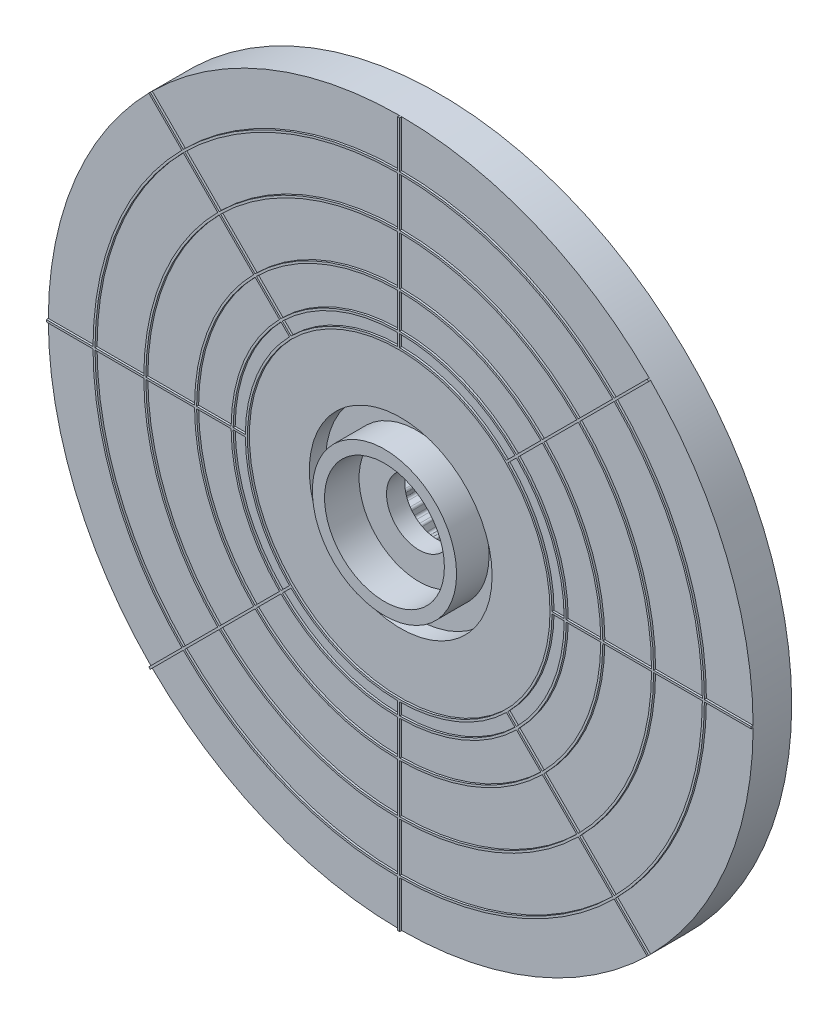
SolidWorks part; units mm, degrees
material "PVC hart"
ref_plane "Ebene vorne" through (0, 0, 0) normal (0, 0, 1) x (1, 0, 0)
ref_plane "Ebene oben" through (0, 0, 0) normal (0, 1, 0) x (1, 0, 0)
ref_plane "Ebene rechts" through (0, 0, 0) normal (1, 0, 0) x (0, 0, -1)
sketch "Skizze5" plane through (0, 0, 0) normal (1, 0, 0) x (0, 0, -1)
  line L0 (0, 0) -> (31.9699, 0) construction
  line L1 (0.75, 4.1) -> (3.1, 4.1)
  line L2 (3.1, 4.1) -> (3.1, 2.9)
  line L3 (3.1, 2.9) -> (0, 2.9)
  line L4 (0, 2.9) -> (0, 1.6)
  line L5 (0, 1.6) -> (-0.9, 1.6)
  line L6 (-0.9, 1.6) -> (-0.9, 2.95)
  line L7 (-0.9, 2.95) -> (-2.6, 2.95)
  line L8 (-2.6, 2.95) -> (-2.6, 3.55)
  line L9 (-2.6, 3.55) -> (-1, 3.55)
  line L10 (-1, 3.55) -> (-1, 4.5)
  line L11 (-1, 4.5) -> (-1.8, 4.5)
  line L12 (-1.8, 4.5) -> (-1.8, 20)
  line L13 (-1.8, 20) -> (0.1, 20)
  line L14 (0.1, 20) -> (0.1, 4.75)
  line L15 (0, 1.6) -> (0, 0) construction
  line L16 (0.1, 4.75) -> (0.75, 4.1)
  dimension "D1" = 8.2
  dimension "D2" = 5.8
  dimension "D3" = 135
  dimension "D4" = 3
  dimension "D5" = 1.9
  dimension "D6" = 9
  dimension "D7" = 7.1
  dimension "D8" = 5.9
  dimension "D9" = 3.2
  dimension "D10" = 3.1
  dimension "D11" = 5.7
  dimension "D12" = 1.7
  dimension "D13" = 40
  dimension "D14" = 0.8
  dimension "D15" = 9.5
revolve "Rotation2" add sketch "Skizze5" angle 360 about L0
ref_axis "Rotationsachse" through (0, 0, 0) along (0, 0, 1)
sketch "Skizze4" plane through (0, 0, -3.1) normal (0, 0, 1) x (1, 0, 0)
  line L0 (0, 0) -> (-0.3635, 2.8771) construction
  line L1 (-0.2786, 2.847) -> (-0.0723, 2.6309)
  line L2 (0.2786, 2.847) -> (0.0723, 2.6309)
  line L3 (0.3635, 2.8771) -> (0, 0) construction
  line L4 (0, 2.9) -> (0, 0) construction
  circle A0 centre (0, 0) radius 2.9 construction
  arc A2 (-0.3635, 2.8771) -> (0.3635, 2.8771) centre (0, 0) cw
  circle A3 centre (0, 0) radius 2.6 construction
  arc A4 (-0.0723, 2.6309) -> (0.0723, 2.6309) centre (0, 2.7) ccw
  arc A5 (-0.3635, 2.8771) -> (-0.2786, 2.847) centre (-0.3509, 2.7779) cw
  arc A6 (0.3635, 2.8771) -> (0.2786, 2.847) centre (0.3509, 2.7779) ccw
  point P14 (0, 2.6)
  dimension "D2" = 5.2
  dimension "D3" = 0.1
  dimension "D1" = 14.4
extrude "Aufsatz-Linear austragen4" add sketch "Skizze4" along normal up to surface (3.1 mm away) up to face at (2.9, 0, 0)
pattern_circular "Kreismuster1" count 25 over 360 about axis through (0, 0, 0) along (0, 0, 1) of "Aufsatz-Linear austragen4"
sketch "Skizze6" plane through (0, 0, 1.8) normal (0, 0, 1) x (1, 0, 0)
  circle A0 centre (0, 0) radius 17.35
  dimension "D1" = 34.7
extrude "Schnitt-Linear austragen1" cut sketch "Skizze6" against normal through all flip side to cut
sketch "Skizze7" plane through (0, 0, 1.8) normal (0, 0, 1) x (1, 0, 0)
  line L0 (0, 17.35) -> (0, 7.5)
  line L1 (7.5, 0) -> (17.35, 0)
  line L2 (0, -7.5) -> (0, -17.35)
  line L3 (-7.5, 0) -> (-17.35, 0)
  line L4 (5.3033, 5.3033) -> (12.2683, 12.2683)
  line L5 (5.3033, -5.3033) -> (12.2683, -12.2683)
  line L6 (-5.3033, -5.3033) -> (-12.2683, -12.2683)
  line L7 (-5.3033, 5.3033) -> (-12.2683, 12.2683)
  line L8 (-17.35, 0) -> (-12.2683, 12.2683) construction
  line L9 (0, 17.35) -> (-12.2683, 12.2683) construction
  line L10 (0, 17.35) -> (12.2683, 12.2683) construction
  line L11 (12.2683, 12.2683) -> (17.35, 0) construction
  line L12 (17.35, 0) -> (12.2683, -12.2683) construction
  line L13 (12.2683, -12.2683) -> (0, -17.35) construction
  line L14 (0, -17.35) -> (-12.2683, -12.2683) construction
  line L15 (-12.2683, -12.2683) -> (-17.35, 0) construction
  circle A0 centre (0, 0) radius 10
  circle A1 centre (0, 0) radius 12.5
  circle A2 centre (0, 0) radius 15
  circle A3 centre (0, 0) radius 7.5
  circle A4 centre (0, 0) radius 8.2
  circle A5 centre (0, 0) radius 17.35 construction
  dimension "D1" = 15
  dimension "D2" = 16.4
  dimension "D3" = 20
  dimension "D4" = 25
  dimension "D5" = 30
extrude "Linear-Austragen-Dünn1" add sketch "Skizze7" along normal blind 0.1 thin contours A3 | A4 | A0 | A1 | A2 | L0 | L7 | L3 | L6 | L2 | L5 | L1 | L4 thin type mid plane wall 0.1
sketch "Skizze9" [suppressed] plane through (0, 0, 1.8) normal (0, 0, 1) x (1, 0, 0)
  line L0 (-4.275, 7.1726) -> (-2.3589, 17.3923)
  line L1 (2.3589, 17.3923) -> (4.275, 7.1726)
  line L2 (0, 16.95) -> (0, -16.95) construction
  line L3 (-4.275, -7.1726) -> (-2.3589, -17.3923)
  line L4 (7.65, 0) -> (10.7, 0) construction
  line L5 (10.7, 0) -> (13.75, 0) construction
  line L6 (13.75, 0) -> (16.95, 0)
  line L7 (16.95, 0) -> (20, 0) construction
  line L8 (2.3589, -17.3923) -> (4.275, -7.1726)
  arc A0 (-2.3589, 17.3923) -> (2.3589, 17.3923) centre (0, 16.95) cw
  circle A1 centre (0, 0) radius 20 construction
  circle A2 centre (0, -7.65) radius 0.9
  circle A3 centre (0, 0) radius 16.95 construction
  circle A4 centre (0, 0) radius 8.35 construction
  circle A6 centre (0, 0) radius 6.75 construction
  circle A7 centre (0, 16.95) radius 0.9
  circle A8 centre (0, 13.75) radius 0.9
  circle A9 centre (0, 10.7) radius 0.9
  circle A10 centre (0, 7.65) radius 0.9
  circle A11 centre (0, 0) radius 13.75 construction
  circle A12 centre (0, 0) radius 10.7 construction
  circle A13 centre (0, 0) radius 7.65 construction
  circle A14 centre (0, -10.7) radius 0.9
  circle A15 centre (0, -13.75) radius 0.9
  circle A16 centre (0, -16.95) radius 0.9
  arc A17 (-2.3589, -17.3923) -> (2.3589, -17.3923) centre (0, -16.95) ccw
  arc A18 (-4.275, 7.1726) -> (-4.275, -7.1726) centre (33.9807, 0) ccw
  arc A19 (4.275, -7.1726) -> (4.275, 7.1726) centre (-33.9807, 0) ccw
  dimension "D1" = 2.4
  dimension "D3" = 15.3
  dimension "D4" = 16.7
  dimension "D6" = 13.5
  dimension "D8" = 1.8
  dimension "D2" = 8.55
  dimension "D7" = 3.2
extrude "2er" [suppressed] cut sketch "Skizze9" against normal through all flip side to cut
sketch "Skizze8" [suppressed] plane through (0, 0, 1.8) normal (0, 0, 1) x (1, 0, 0)
  line L0 (-4.275, 7.1726) -> (-2.3589, 17.3923)
  line L1 (2.3589, 17.3923) -> (4.275, 7.1726)
  line L2 (0, 16.95) -> (0, -16.95) construction
  line L3 (0, 0) -> (14.1421, 14.1421) construction
  line L4 (7.65, 0) -> (10.7, 0) construction
  line L5 (10.7, 0) -> (13.75, 0) construction
  line L6 (13.75, 0) -> (16.95, 0)
  line L7 (16.95, 0) -> (20, 0) construction
  line L8 (7.1726, 4.275) -> (17.3923, 2.3589)
  line L9 (17.3923, -2.3589) -> (7.1726, -4.275)
  line L10 (4.275, -7.1726) -> (2.3589, -17.3923)
  line L11 (-2.3589, -17.3923) -> (-4.275, -7.1726)
  line L12 (-7.1726, -4.275) -> (-17.3923, -2.3589)
  line L13 (-17.3923, 2.3589) -> (-7.1726, 4.275)
  arc A0 (-2.3589, 17.3923) -> (2.3589, 17.3923) centre (0, 16.95) cw
  arc A1 (4.275, 7.1726) -> (7.1726, 4.275) centre (6.3522, 6.3522) ccw
  circle A2 centre (0, 0) radius 8.9834 construction
  circle A3 centre (0, 0) radius 16.95 construction
  circle A4 centre (0, 0) radius 8.35 construction
  circle A5 centre (0, 0) radius 20 construction
  circle A6 centre (0, 0) radius 6.75 construction
  circle A7 centre (0, 16.95) radius 0.9
  circle A8 centre (0, 13.75) radius 0.9
  circle A9 centre (0, 10.7) radius 0.9
  circle A10 centre (0, 7.65) radius 0.9
  circle A11 centre (0, 0) radius 13.75 construction
  circle A12 centre (0, 0) radius 10.7 construction
  circle A13 centre (0, 0) radius 7.65 construction
  arc A14 (17.3923, 2.3589) -> (17.3923, -2.3589) centre (16.95, 0) cw
  circle A15 centre (16.95, 0) radius 0.9
  circle A16 centre (13.75, 0) radius 0.9
  circle A17 centre (10.7, 0) radius 0.9
  circle A18 centre (7.65, 0) radius 0.9
  arc A19 (7.1726, -4.275) -> (4.275, -7.1726) centre (6.3522, -6.3522) ccw
  arc A20 (2.3589, -17.3923) -> (-2.3589, -17.3923) centre (0, -16.95) cw
  circle A21 centre (0, -16.95) radius 0.9
  circle A22 centre (0, -13.75) radius 0.9
  circle A23 centre (0, -10.7) radius 0.9
  circle A24 centre (0, -7.65) radius 0.9
  arc A25 (-4.275, -7.1726) -> (-7.1726, -4.275) centre (-6.3522, -6.3522) ccw
  arc A26 (-17.3923, -2.3589) -> (-17.3923, 2.3589) centre (-16.95, 0) cw
  circle A27 centre (-16.95, 0) radius 0.9
  circle A28 centre (-13.75, 0) radius 0.9
  circle A29 centre (-10.7, 0) radius 0.9
  circle A30 centre (-7.65, 0) radius 0.9
  arc A31 (-7.1726, 4.275) -> (-4.275, 7.1726) centre (-6.3522, 6.3522) ccw
  point P77 (0, 0)
  dimension "D1" = 2.4
  dimension "D3" = 15.3
  dimension "D4" = 16.7
  dimension "D6" = 13.5
  dimension "D8" = 1.8
  dimension "D2" = 8.55
  dimension "D5" = 45
  dimension "D7" = 3.2
  dimension "D9" = 4
extrude "4er" [suppressed] cut sketch "Skizze8" against normal through all flip side to cut
sketch "Skizze10" [suppressed] plane through (0, 0, 1.8) normal (0, 0, 1) x (1, 0, 0)
  line L0 (7.6, 0) -> (9.9, 0) construction
  line L1 (9.9, 0) -> (12.75, 0) construction
  line L2 (0, 12.75) -> (0, -12.75) construction
  line L3 (-3.4, 5.889) -> (-2.3761, 13.088)
  line L4 (2.3761, 13.088) -> (3.4, 5.889)
  line L5 (-3.4, 5.889) -> (0, 0) construction
  line L6 (0, 0) -> (3.4, 5.889) construction
  line L7 (-3.4, 5.889) -> (3.4, 5.889) construction
  line L8 (3.4, 5.889) -> (10.1465, 8.6017)
  line L9 (12.5225, 4.4862) -> (6.8, 0)
  line L10 (6.8, 0) -> (12.5225, -4.4862)
  line L11 (10.1465, -8.6017) -> (3.4, -5.889)
  line L12 (3.4, -5.889) -> (2.3761, -13.088)
  line L13 (-2.3761, -13.088) -> (-3.4, -5.889)
  line L14 (-3.4, -5.889) -> (-10.1465, -8.6017)
  line L15 (-12.5225, -4.4862) -> (-6.8, 0)
  line L16 (-6.8, 0) -> (-12.5225, 4.4862)
  line L17 (-10.1465, 8.6017) -> (-3.4, 5.889)
  circle A0 centre (0, 0) radius 7.6 construction
  circle A1 centre (0, 0) radius 9.9 construction
  circle A2 centre (0, 0) radius 12.75 construction
  circle A3 centre (0, 7.6) radius 0.9
  circle A4 centre (0, 9.9) radius 0.9
  circle A5 centre (0, 12.75) radius 0.9
  arc A6 (-2.3761, 13.088) -> (2.3761, 13.088) centre (0, 12.75) cw
  circle A7 centre (0, 0) radius 6.8 construction
  circle A8 centre (6.5818, 3.8) radius 0.9
  circle A9 centre (8.5737, 4.95) radius 0.9
  circle A10 centre (11.0418, 6.375) radius 0.9
  arc A11 (10.1465, 8.6017) -> (12.5225, 4.4862) centre (11.0418, 6.375) cw
  circle A12 centre (6.5818, -3.8) radius 0.9
  circle A13 centre (8.5737, -4.95) radius 0.9
  circle A14 centre (11.0418, -6.375) radius 0.9
  arc A15 (12.5225, -4.4862) -> (10.1465, -8.6017) centre (11.0418, -6.375) cw
  circle A16 centre (0, -7.6) radius 0.9
  circle A17 centre (0, -9.9) radius 0.9
  circle A18 centre (0, -12.75) radius 0.9
  arc A19 (2.3761, -13.088) -> (-2.3761, -13.088) centre (0, -12.75) cw
  circle A20 centre (-6.5818, -3.8) radius 0.9
  circle A21 centre (-8.5737, -4.95) radius 0.9
  circle A22 centre (-11.0418, -6.375) radius 0.9
  arc A23 (-10.1465, -8.6017) -> (-12.5225, -4.4862) centre (-11.0418, -6.375) cw
  circle A24 centre (-6.5818, 3.8) radius 0.9
  circle A25 centre (-8.5737, 4.95) radius 0.9
  circle A26 centre (-11.0418, 6.375) radius 0.9
  arc A27 (-12.5225, 4.4862) -> (-10.1465, 8.6017) centre (-11.0418, 6.375) cw
  point P72 (0, 0)
  dimension "D1" = 1.8
  dimension "D3" = 15.2
  dimension "D4" = 2.4
  dimension "D5" = 19.8
  dimension "D6" = 25.5
  dimension "D7" = 6
  dimension "D2" = 6.8
extrude "Schnitt-Linear austragen2" [suppressed] cut sketch "Skizze10" against normal through all flip side to cut
